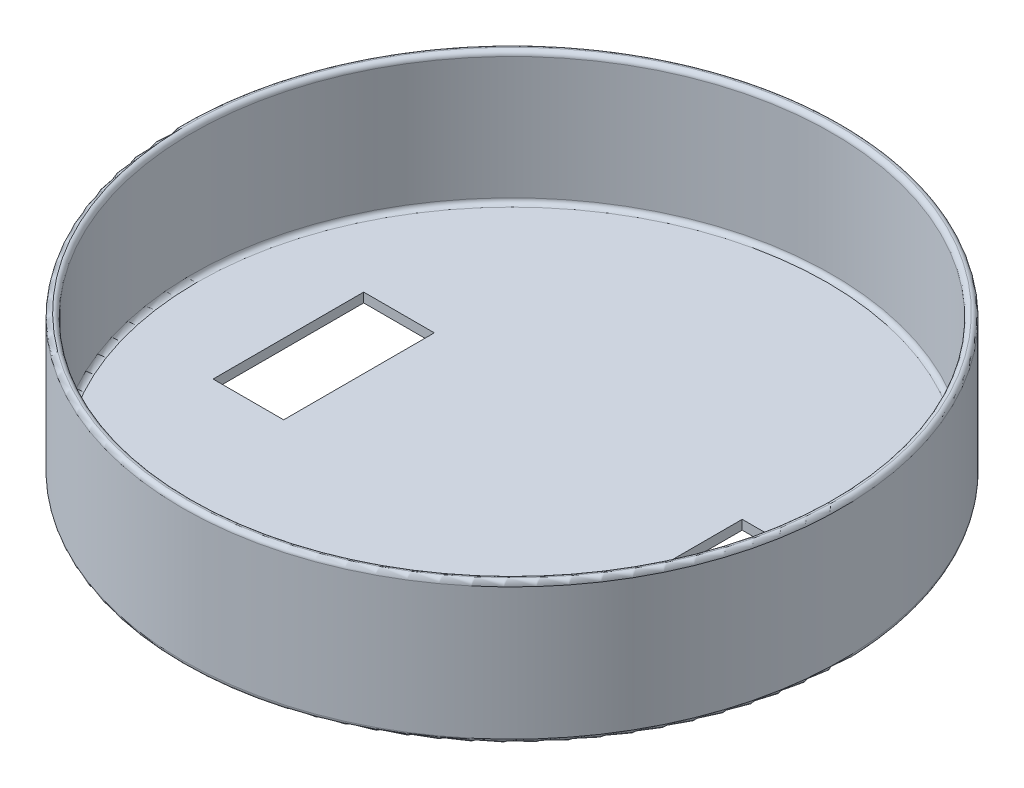
SolidWorks part; units mm, degrees
material "Aleación 1060"
ref_plane "Alzado" through (0, 0, 0) normal (0, 0, 1) x (1, 0, 0)
ref_plane "Planta" through (0, 0, 0) normal (0, 1, 0) x (1, 0, 0)
ref_plane "Vista lateral" through (0, 0, 0) normal (1, 0, 0) x (0, 0, -1)
sketch "Croquis1" plane through (0, 0, 0) normal (0, 1, 0) x (1, 0, 0)
  circle A0 centre (0, 0) radius 35
  dimension "D1" = 70
extrude "Saliente-Extruir1" add sketch "Croquis1" along normal blind 15
sketch "Croquis2" plane through (0, 15, 0) normal (0, 1, 0) x (1, 0, 0)
  circle A0 centre (0, 0) radius 34
  dimension "D1" = 68
extrude "Cortar-Extruir1" cut sketch "Croquis2" against normal offset from surface (14 mm away) 1 up to face at (0, 0, 35)
fillet "Redondeo1" radius 0.5 1 edges at (0, 0, 35)
fillet "Redondeo5" radius 0.5 3 edges at (0, 15, 35) (0, 15, 34) (0, 1, 34)
sketch "Croquis3" plane through (0, 0, 0) normal (0, -1, 0) x (1, 0, 0)
  line L0 (0, 0) -> (20, 0) construction
  line L1 (17.25, -7.2) -> (22.75, -7.2)
  line L2 (17.25, -7.2) -> (17.25, 7.2)
  line L3 (17.25, 7.2) -> (22.75, 7.2)
  line L4 (22.75, -7.2) -> (22.75, 7.2)
  line L5 (17.25, -7.2) -> (22.75, 7.2) construction
  line L6 (17.25, 7.2) -> (22.75, -7.2) construction
  line L7 (0, 0) -> (-20, 0) construction
  line L8 (-23.75, 8) -> (-16.25, 8)
  line L9 (-23.75, 8) -> (-23.75, -8)
  line L10 (-23.75, -8) -> (-16.25, -8)
  line L11 (-16.25, 8) -> (-16.25, -8)
  line L12 (-23.75, 8) -> (-16.25, -8) construction
  line L13 (-23.75, -8) -> (-16.25, 8) construction
  point P0 (20, 0)
  dimension "D1" = 5.5
  dimension "D2" = 14.4
  dimension "D3" = 20
  dimension "D4" = 20
  dimension "D5" = 7.5
  dimension "D6" = 16
extrude "Cortar-Extruir2" cut sketch "Croquis3" against normal up to next
